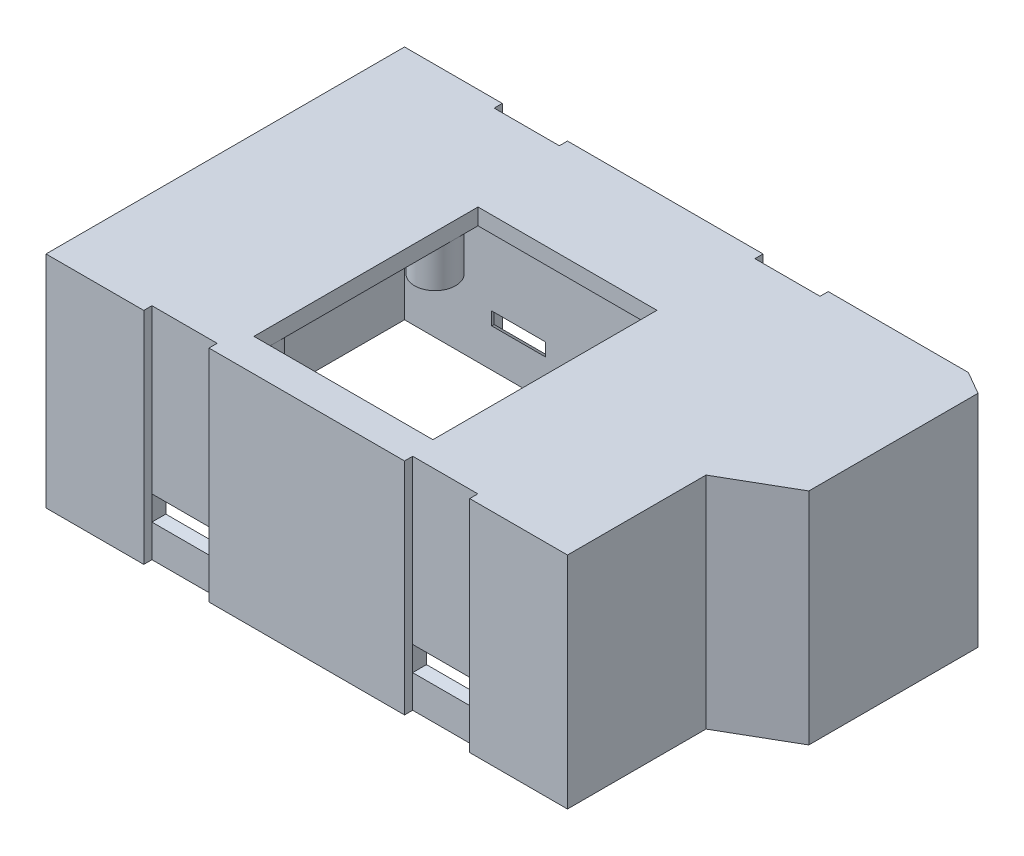
SolidWorks part; units mm, degrees
ref_plane "Front Plane" through (0, 0, 0) normal (0, 0, 1) x (1, 0, 0)
ref_plane "Top Plane" through (0, 0, 0) normal (0, 1, 0) x (1, 0, 0)
ref_plane "Right Plane" through (0, 0, 0) normal (1, 0, 0) x (0, 0, -1)
sketch "Sketch1" plane through (0, 0, 0) normal (0, 1, 0) x (1, 0, 0)
  line L0 (-32, 22) -> (-20, 22)
  line L1 (-20, 22) -> (-20, 21)
  line L2 (-20, 21) -> (-12, 21)
  line L3 (-12, 21) -> (-12, 22)
  line L4 (-12, 22) -> (12, 22)
  line L5 (12, 22) -> (12, 21)
  line L6 (12, 21) -> (20, 21)
  line L7 (20, 21) -> (20, 22)
  line L8 (20, 22) -> (32, 22)
  line L9 (32, 22) -> (32, -22)
  line L10 (32, -22) -> (20, -22)
  line L11 (20, -22) -> (20, -21)
  line L12 (20, -21) -> (12, -21)
  line L13 (12, -21) -> (12, -22)
  line L14 (12, -22) -> (-12, -22)
  line L15 (-12, -22) -> (-12, -21)
  line L16 (-12, -21) -> (-20, -21)
  line L17 (-20, -21) -> (-20, -22)
  line L18 (-20, -22) -> (-32, -22)
  line L19 (-32, -22) -> (-32, 22)
  line L20 (-30, 20) -> (30, 20)
  line L21 (-30, 20) -> (-30, -20)
  line L22 (-30, -20) -> (30, -20)
  line L23 (30, 20) -> (30, -20)
  line L24 (-30, 20) -> (30, -20) construction
  line L25 (-30, -20) -> (30, 20) construction
  point P20 (0.3143, -0.435)
  point P25 (0, 0)
  point P26 (0, 0)
  point P27 (-20, -21.5)
  point P28 (0, 0)
  point P29 (0, 0)
  point P30 (0, 0)
  point P32 (0, 0)
  dimension "D1" = 2
  dimension "D2" = 1
  dimension "D3" = 2
  dimension "D4" = 2
  dimension "D5" = 64
  dimension "D6" = 40
  dimension "D7" = 8
  dimension "D8" = 12
  dimension "D9" = 24
  dimension "D10" = 24
  dimension "D11" = 12
extrude "Boss-Extrude1" add sketch "Sketch1" along normal blind 27
sketch "Sketch2" plane through (0, 0, 21) normal (0, 0, 1) x (1, 0, 0)
  line L0 (-20, 0) -> (-12, 0) construction
  line L1 (-20, 7) -> (-12, 7)
  line L2 (-20, 7) -> (-20, 4)
  line L3 (-20, 4) -> (-12, 4)
  line L4 (-12, 7) -> (-12, 4)
  line L5 (-20, 7) -> (-12, 4) construction
  line L6 (-20, 4) -> (-12, 7) construction
  line L8 (-12, 27) -> (-12, 0) construction
  point P0 (-16, 5.5)
  dimension "D1" = 7
  dimension "D2" = 3
extrude "Cut-Extrude1" cut sketch "Sketch2" against normal blind 1 draft 35
mirror "Mirror1" about plane through (0, 0, 0) normal (1, 0, 0) of "Cut-Extrude1"
mirror "Mirror2" about plane through (0, 0, 0) normal (0, 0, 1) of "Mirror1", "Cut-Extrude1"
extrude "Boss-Extrude2" add sketch "Sketch1<3>" against normal blind 2 from surface contours L23 L20 L21 L22 region at (0, 0, 0) starting at face at (0, 27, 0)
sketch "Sketch1<3>" plane through (0, 0, 0) normal (0, 1, 0) x (1, 0, 0) same geometry as "Sketch1"
sketch "Sketch3" plane through (0, 25, 0) normal (0, -1, 0) x (1, 0, 0)
  line L0 (-30, 20) -> (30, 20) construction
  line L1 (-17, 18) -> (18, 18) construction
  line L2 (-17, 18) -> (-17, -9.5) construction
  line L3 (-17, -9.5) -> (18, -9.5) construction
  line L4 (18, 18) -> (18, -9.5) construction
  line L5 (-17, 18) -> (18, -9.5) construction
  line L6 (-17, -9.5) -> (18, 18) construction
  line L7 (-30, -20) -> (-30, 20) construction
  line L8 (-13, 15.25) -> (14, 15.25) construction
  line L9 (-13, 15.25) -> (-13, -6.75) construction
  line L10 (-13, -6.75) -> (14, -6.75) construction
  line L11 (14, 15.25) -> (14, -6.75) construction
  line L12 (-13, 15.25) -> (14, -6.75) construction
  line L13 (-13, -6.75) -> (14, 15.25) construction
  line L15 (-10.4803, 18) -> (11.4803, 18)
  line L16 (-10.4803, 18) -> (-10.4803, -9.5)
  line L17 (-10.4803, -9.5) -> (11.4803, -9.5)
  line L18 (11.4803, 18) -> (11.4803, -9.5)
  line L19 (-10.4803, 18) -> (11.4803, -9.5) construction
  line L20 (-10.4803, -9.5) -> (11.4803, 18) construction
  circle A0 centre (-13, 15.25) radius 1.4
  circle A1 centre (-13, 15.25) radius 2.5
  circle A2 centre (14, 15.25) radius 1.4
  circle A3 centre (14, 15.25) radius 2.5
  circle A4 centre (-13, -6.75) radius 1.4
  circle A5 centre (-13, -6.75) radius 2.5197
  circle A6 centre (14, -6.75) radius 1.4
  circle A7 centre (14, -6.75) radius 2.5197
  point P0 (0.5, 4.25)
  point P7 (0.5, 4.25)
  point P18 (0.5, 4.25)
  point P30 (0, 0)
  dimension "D7" = 2.8
  dimension "D8" = 5
  dimension "D1" = 35
  dimension "D2" = 27.5
  dimension "D3" = 2
  dimension "D4" = 27
  dimension "D5" = 22
  dimension "D6" = 13
extrude "Cut-Extrude2" cut sketch "Sketch3" against normal blind 2 contours L18 L15 L16 L17 region at (0.5, 25, 4.25)
extrude "Boss-Extrude3" add sketch "Sketch3<3>" along normal blind 5 contours A1 A0 | A5 A4 | A7 A6 | A3 A2 region at (14, 25, -4.3016) region at (-15.4484, 25, -6.75) region at (-15.4293, 25, 15.25) region at (11.5707, 25, 15.25)
sketch "Sketch3<3>" plane through (0, 25, 0) normal (0, -1, 0) x (1, 0, 0) same geometry as "Sketch3"
sketch "Sketch4" plane through (32, 0, 0) normal (1, 0, 0) x (0, 0, -1)
  line L1 (0, 27) -> (20, 27)
  line L2 (0, 27) -> (0, 0)
  line L3 (0, 0) -> (20, 0)
  line L4 (20, 27) -> (20, 0)
  line L5 (0, 27) -> (20, 0) construction
  line L6 (0, 0) -> (20, 27) construction
  line L8 (-22, 0) -> (22, 0) construction
  line L9 (-22, 27) -> (22, 27) construction
  line L10 (22, 27) -> (22, 0) construction
  point P0 (10, 13.5)
  point P5 (9.4704, 13.5)
  dimension "D1" = 20
  dimension "D2" = 2
extrude "Boss-Extrude4" add sketch "Sketch4" along normal blind 8
chamfer "Chamfer1" distance 5 angle 60 2 edges at (32, 13.5, -20) (32, 13.5, 0) first distance on face at (32, 13.5, -21) first distance on face at (32, 13.5, 11)
sketch "Sketch5" plane through (0, 0, 0) normal (0, -1, 0) x (1, 0, 0)
  line L0 (-30, -20) -> (30, -20) construction
  line L1 (30, 0) -> (38, 0)
  line L2 (30, 0) -> (30, -20)
  line L3 (30, -20) -> (38, -20)
  line L4 (38, 0) -> (38, -20)
  line L5 (30, 0) -> (38, -20) construction
  line L6 (30, -20) -> (38, 0) construction
  line L7 (30, -20) -> (30, 20) construction
  line L8 (40, 0.3812) -> (40, -20.3812) construction
  point P0 (34, -10)
  point P5 (0, 0)
  dimension "D1" = 20
  dimension "D2" = 2
extrude "Cut-Extrude3" cut sketch "Sketch5" against normal up to surface (25 mm away) up to face at (14, 25, 17.75)
sketch "Sketch6" plane through (0, 25, 0) normal (0, -1, 0) x (1, 0, 0)
  line L0 (38, -20) -> (-30, -20) construction
  line L1 (18, 20) -> (30, 20)
  line L2 (18, 20) -> (18, -20)
  line L3 (18, -20) -> (30, -20)
  line L4 (30, 20) -> (30, -20)
  line L5 (18, 20) -> (30, -20) construction
  line L6 (18, -20) -> (30, 20) construction
  line L7 (-30, 20) -> (30, 20) construction
  line L8 (30, 20) -> (30, 0) construction
  point P0 (24, 0)
  dimension "D1" = 12
extrude "Cut-Extrude5" cut sketch "Sketch6" against normal blind 1.5
